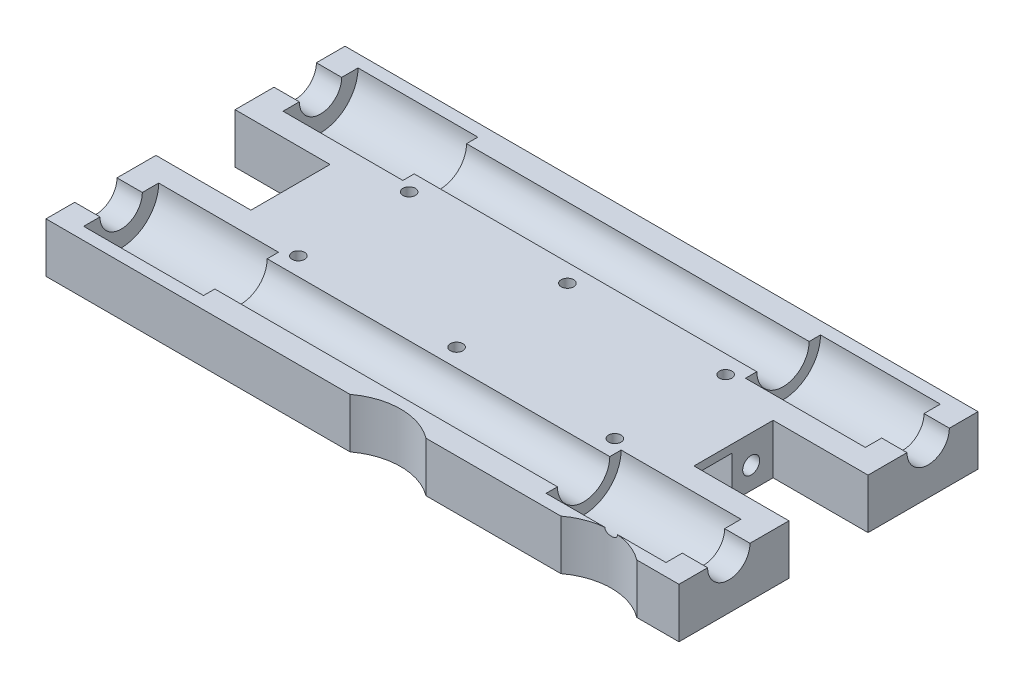
SolidWorks part; units mm, degrees
ref_plane "Front Plane" through (0, 0, 0) normal (0, 0, 1) x (1, 0, 0)
ref_plane "Top Plane" through (0, 0, 0) normal (0, 1, 0) x (1, 0, 0)
ref_plane "Right Plane" through (0, 0, 0) normal (1, 0, 0) x (0, 0, -1)
ref_axis "Axis X" through (-88.99, 0, 0) along (1, 0, 0)
ref_axis "Axis Y" through (0, 55, 0) along (0, -1, 0)
ref_axis "Axis Z" through (0, 0, -88.99) along (0, 0, 1)
sketch "Sketch1" plane through (0, 0, 0) normal (0, 1, 0) x (1, 0, 0)
  line L1 (-63.5, -30) -> (63.5, -30)
  line L2 (-63.5, -30) -> (-63.5, 30)
  line L3 (-63.5, 30) -> (63.5, 30)
  line L4 (63.5, -30) -> (63.5, 30)
  line L5 (-63.5, -30) -> (63.5, 30) construction
  line L6 (-63.5, 30) -> (63.5, -30) construction
  point P0 (0, 0)
  dimension "D1" = 60
  dimension "D2" = 127
extrude "Boss-Extrude1" add sketch "Sketch1" along normal blind 10
sketch "Sketch3" plane through (-63.5, 0, 0) normal (-1, 0, 0) x (0, 0, 1)
  line L0 (0, 0) -> (0, 19.22) construction
  line L1 (0, -5.5) -> (0, 5.5) construction
  line L4 (-30, 10) -> (30, 10) construction
  circle A0 centre (-20, 10) radius 7.525
  circle A1 centre (20, 10) radius 7.525
  dimension "D1" = 15.05
  dimension "D2" = 40
  dimension "D3" = 2.475
extrude "Cut-Extrude1" cut sketch "Sketch3" against normal blind 24.05 from offset 5.08 contours A0 | A1 offset against normal yes
mirror "Mirror1" about plane through (0, 0, 0) normal (1, 0, 0) of "Cut-Extrude1"
sketch "Sketch4" plane through (-58.42, 0, 0) normal (1, 0, 0) x (0, 0, -1)
  circle A0 centre (20, 10) radius 4.25
  arc A1 (12.475, 10) -> (27.525, 10) centre (20, 10) ccw construction
  dimension "D1" = 8.5
extrude "Cut-Extrude2" cut sketch "Sketch4" against normal up to next and the other way up to surface other way up to face at (63.5, 5, 0)
mirror "Mirror2" about plane through (0, 0, 0) normal (0, 0, 1) of "Cut-Extrude2"
sketch "Sketch5" plane through (34.37, 0, 0) normal (1, 0, 0) x (0, 0, -1)
  arc A0 (-24.25, 10) -> (-15.75, 10) centre (-20, 10) ccw construction
  circle A1 centre (-20, 10) radius 4.25
  circle A2 centre (-20, 10) radius 5.25
  dimension "D1" = 1
extrude "Cut-Extrude3" cut sketch "Sketch5" against normal up to surface (68.74 mm away) up to face at (-34.37, 7.0563, 20)
mirror "Mirror3" about plane through (0, 0, 0) normal (0, 0, 1) of "Cut-Extrude3"
sketch "Sketch6" plane through (-63.5, 0, 0) normal (-1, 0, 0) x (0, 0, 1)
  line L0 (-30, 0) -> (30, 0) construction
  line L1 (-7.9375, 0) -> (7.9375, 0)
  line L2 (-7.9375, 0) -> (-7.9375, 10)
  line L3 (-7.9375, 10) -> (7.9375, 10)
  line L4 (7.9375, 0) -> (7.9375, 10)
  line L5 (0, 0) -> (0, 21.817) construction
  line L6 (0, -5.5) -> (0, 5.5) construction
  line L7 (-15.75, 10) -> (15.75, 10) construction
  dimension "D2" = 15.875
extrude "Cut-Extrude4" cut sketch "Sketch6" against normal blind 19.05
mirror "Mirror4" about plane through (0, 0, 0) normal (1, 0, 0) of "Cut-Extrude4"
hole_wizard "M3 Clearance Hole1" positions "Sketch8" profile "Sketch7" hole size "M3" standard "ANSI Metric" end condition up to next
sketch "Sketch8" plane through (-44.45, 0, 0) normal (-1, 0, 0) x (0, 0, 1)
  line L0 (-7.9375, 10) -> (-7.9375, 0) construction
  line L2 (-30, 0) -> (-7.9375, 0) construction
  point P0 (-3.5375, 4.4)
  dimension "D1" = 4.4
  dimension "D2" = 4.4
sketch "Sketch7" plane through (-44.45, 4.4, -3.5375) normal (0, 1, 0) x (0, 0, 1)
  line L0 (0, 0) -> (0, 88.9)
  line L1 (0, 88.9) -> (1.7, 88.9)
  line L2 (1.7, 88.9) -> (1.7, 0)
  line L5 (1.7, 0) -> (0, 0)
  line L11 (0, -6.35) -> (0, 107.95) construction
  dimension "Thru Hole Dia." = 3.4
  dimension "Thru Hole Depth" = 88.9
sketch "Sketch9" plane through (-44.45, 0, 0) normal (-1, 0, 0) x (0, 0, 1)
  line L0 (-7.9375, 0) -> (7.9375, 0) construction
  line L1 (-0.7875, 0) -> (-0.7875, 5.9877)
  line L2 (-0.7875, 5.9877) -> (-3.5375, 7.5754)
  line L3 (-3.5375, 7.5754) -> (-6.2875, 5.9877)
  line L4 (-6.2875, 5.9877) -> (-6.2875, 0)
  line L5 (-6.2875, 0) -> (-0.7875, 0)
  line L8 (-6.2875, 2.8123) -> (-3.5375, 1.2246) [skipped]
  line L9 (-3.5375, 1.2246) -> (-0.7875, 2.8123) [skipped]
  circle A0 centre (-3.5375, 4.4) radius 2.75 construction
  dimension "D1" = 5.5
extrude "Cut-Extrude5" cut sketch "Sketch9" against normal blind 5 from offset 6.35 offset against normal yes
mirror "Mirror5" about plane through (0, 0, 0) normal (1, 0, 0) of "Cut-Extrude5"
hole_wizard "M3x0.5 Tapped Hole1" positions "Sketch11" profile "Sketch10" tap size "M3x0.5" standard "ANSI Metric" end condition up to next
sketch "Sketch11" plane through (0, 10, 0) normal (0, 1, 0) x (1, 0, 0)
  line L0 (0, -5.5) -> (0, 5.5) construction
  line L1 (0, 0) -> (0, -42.9729) construction
  line L3 (0, 0) -> (76.4578, 0) construction
  line L4 (-5.5, 0) -> (5.5, 0) construction
  point P0 (-31.75, -11.1125)
  point P2 (31.75, -11.1125)
  point P4 (-31.75, 11.1125)
  point P6 (31.75, 11.1125)
  point P8 (0, -11.1125)
  point P12 (0, 11.1125)
  dimension "D1" = 22.225
  dimension "D2" = 31.75
sketch "Sketch10" plane through (-31.75, 10, 11.1125) normal (1, 0, 0) x (0, 0, 1)
  line L0 (0, 0) -> (0, 10)
  line L1 (0, 10) -> (1.25, 10)
  line L2 (1.25, 10) -> (1.25, 0)
  line L5 (1.25, 0) -> (0, 0)
  line L11 (0, -6.35) -> (0, 107.95) construction
  dimension "Thread Major Dia." = 2.5
  dimension "Thru Tap Drill Depth" = 10
sketch "Sketch12" plane through (-44.45, 0, 0) normal (-1, 0, 0) x (0, 0, 1)
  line L0 (7.9375, 10) -> (-7.9375, 10) construction
  line L1 (7.9375, 0) -> (0.3175, 0)
  line L2 (7.9375, 0) -> (7.9375, 8.4125)
  line L3 (7.9375, 8.4125) -> (0.3175, 8.4125)
  line L4 (0.3175, 0) -> (0.3175, 8.4125)
  dimension "D1" = 7.62
  dimension "D2" = 1.5875
extrude "Cut-Extrude6" cut sketch "Sketch12" against normal through all
sketch "Sketch13" plane through (0, 0, 0) normal (0, -1, 0) x (1, 0, 0)
  line L3 (63.5, 30) -> (63.5, 7.9375) construction
  line L4 (-63.5, 30) -> (63.5, 30) construction
  circle A0 centre (5.1218, 40.16) radius 12.7
  circle A1 centre (47.4218, 40.16) radius 12.7
  dimension "D1" = 42.3
  dimension "D2" = 25.4
  dimension "D3" = 16.0782
  dimension "D4" = 10.16
extrude "Cut-Extrude7" cut sketch "Sketch13" against normal up to next
